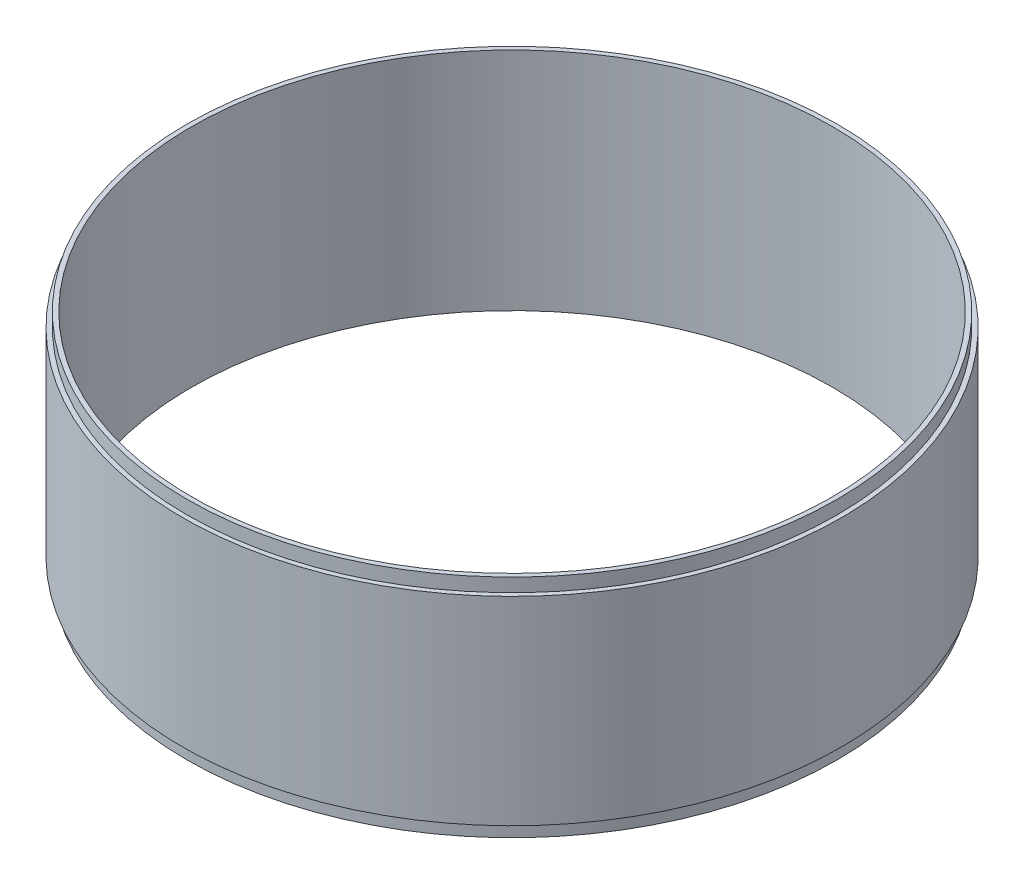
SolidWorks part; units mm, degrees
material "Silica Phenolic"
ref_plane "Piano frontale" through (0, 0, 0) normal (0, 0, 1) x (1, 0, 0)
ref_plane "Piano superiore" through (0, 0, 0) normal (0, 1, 0) x (1, 0, 0)
ref_plane "Piano destro" through (0, 0, 0) normal (1, 0, 0) x (0, 0, -1)
sketch "Schizzo1" plane through (0, 0, 0) normal (0, 0, 1) x (1, 0, 0)
  line L0 (-71, 3) -> (-71, 0)
  line L3 (-72, 50) -> (-71, 50)
  line L8 (0, 0) -> (0, 47.1479) construction
  line L9 (-71, 0) -> (-72, 0)
  line L10 (-72, 0) -> (-72, 3)
  line L11 (-72, 3) -> (-73, 3)
  line L12 (-71, 3) -> (-71, 50)
  line L13 (-73, 3) -> (-73, 47)
  line L14 (-73, 47) -> (-72, 47)
  line L15 (-72, 47) -> (-72, 50)
  dimension "D1" = 1
  dimension "D2" = 3
  dimension "D3" = 3
  dimension "D4" = 1
  dimension "D5" = 1
  dimension "D6" = 50
  dimension "D7" = 146
revolve "Rivoluzione1" add sketch "Schizzo1" angle 360 about L8 region at (-71.9681, 25, 0)
